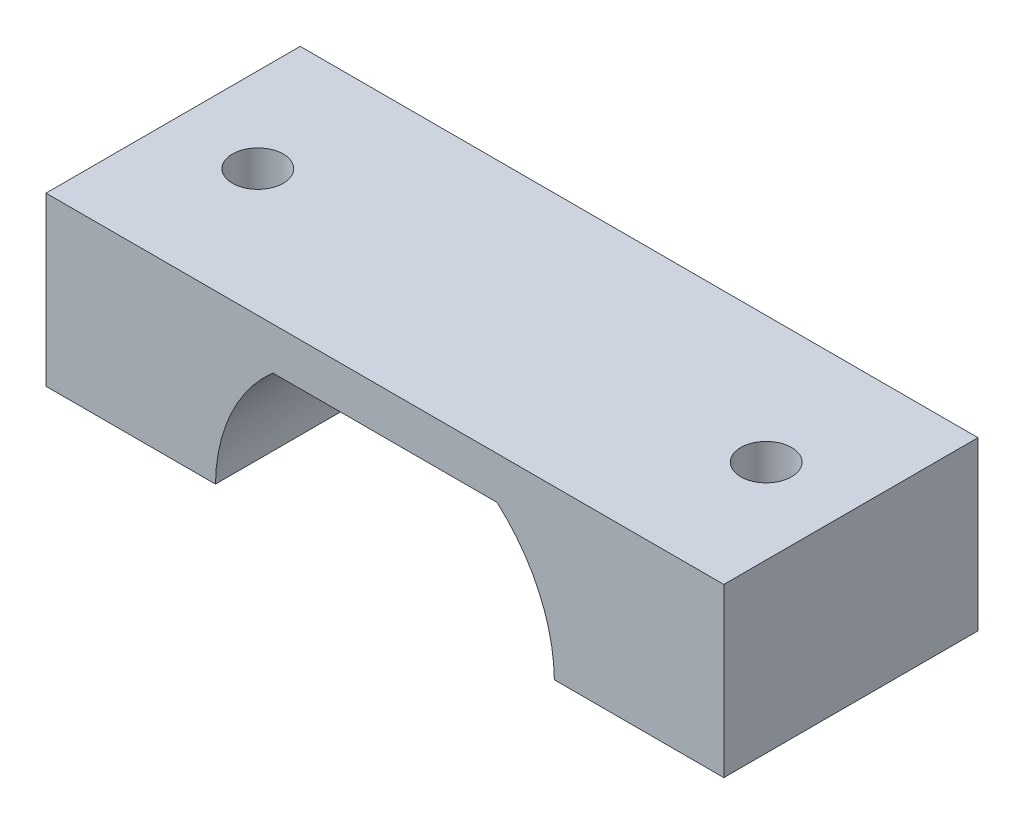
SolidWorks part; units mm, degrees
material "ABS"
ref_plane "Front Plane" through (0, 0, 0) normal (0, 0, 1) x (1, 0, 0)
ref_plane "Top Plane" through (0, 0, 0) normal (0, 1, 0) x (1, 0, 0)
ref_plane "Right Plane" through (0, 0, 0) normal (1, 0, 0) x (0, 0, -1)
sketch "Motor Clamp Outline Sketch" plane through (0, 0, 0) normal (0, 0, 1) x (1, 0, 0)
  line L0 (-20, 0.125) -> (-9.9992, 0.125)
  line L1 (-20, 10) -> (20, 10) construction
  line L2 (-20, 10) -> (-20, 0) construction
  line L3 (-20, 0) -> (20, 0) construction
  line L4 (20, 10) -> (20, 0) construction
  line L5 (-20, 10) -> (20, 0) construction
  line L6 (-20, 0) -> (20, 10) construction
  line L7 (-20, 0.125) -> (-20, 10)
  line L8 (-20, 10) -> (20, 10)
  line L9 (20, 10) -> (20, 0.125)
  line L10 (9.9992, 0.125) -> (20, 0.125)
  line L11 (-6.6144, 7.5) -> (6.6144, 7.5)
  line L12 (-20, 0.125) -> (20, 0.125) construction
  arc A0 (9.9992, 0.125) -> (-9.9992, 0.125) centre (0, 0) ccw construction
  arc A1 (9.9992, 0.125) -> (6.6144, 7.5) centre (0, 0) ccw
  arc A2 (-6.6144, 7.5) -> (-9.9992, 0.125) centre (0, 0) ccw
  point P3 (0, 5)
  dimension "D2" = 20
  dimension "D1" = 40
  dimension "D3" = 10
  dimension "D5" = 2.5
  dimension "D4" = 0.125
extrude "Motor Clamp Outline Solid" add sketch "Motor Clamp Outline Sketch" along normal mid plane 15
sketch "Motor Clamp Mounting Holes Sketch" plane through (0, 10, 0) normal (0, 1, 0) x (1, 0, 0)
  line L0 (-15, 0) -> (15, 0) construction
  circle A0 centre (-15, 0) radius 1.5
  circle A1 centre (15, 0) radius 1.5
  point P4 (0, 0)
  dimension "D1" = 3
  dimension "D2" = 30
extrude "Motor Clamp Mounting Hole Cut" cut sketch "Motor Clamp Mounting Holes Sketch" against normal through all
